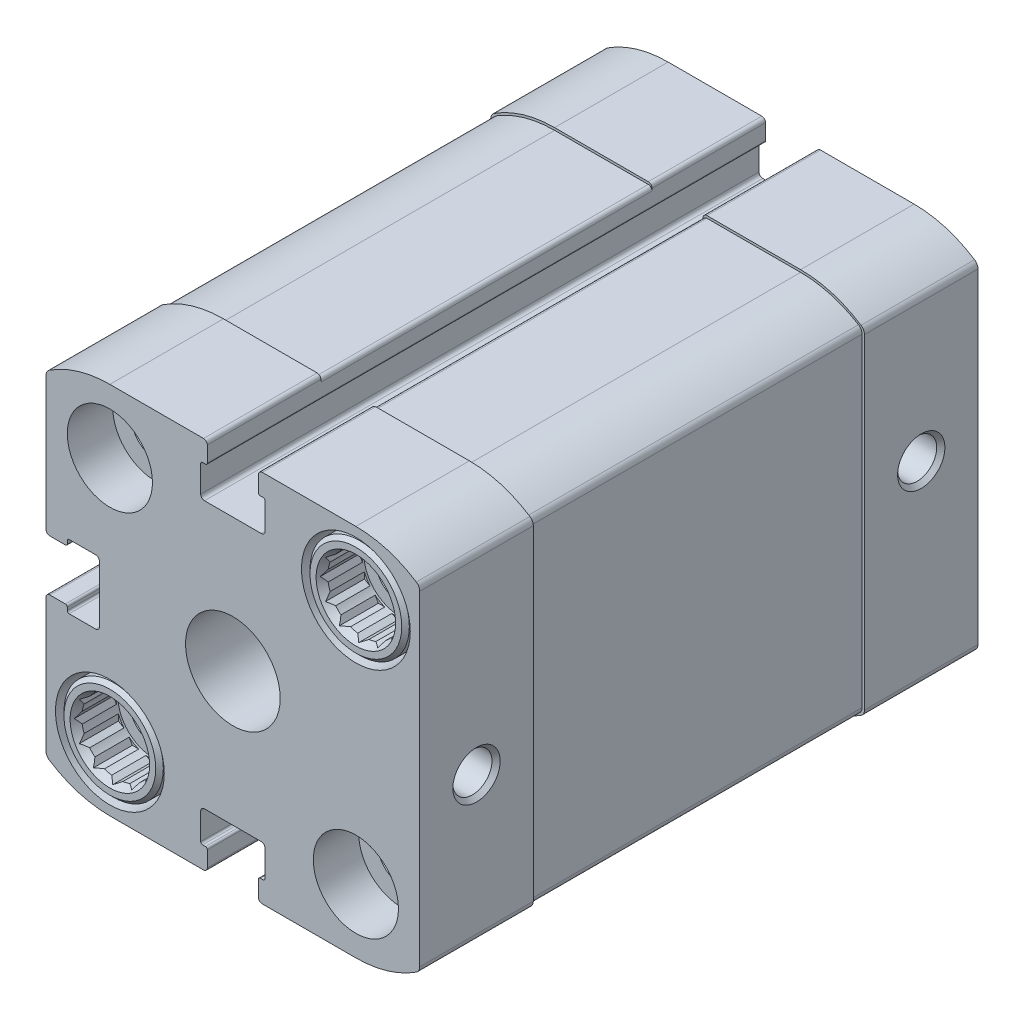
SolidWorks part; units mm, degrees
ref_plane "Ebene vorne" through (0, 0, 0) normal (0, 0, 1) x (1, 0, 0)
ref_plane "Ebene oben" through (0, 0, 0) normal (0, 1, 0) x (1, 0, 0)
ref_plane "Ebene rechts" through (0, 0, 0) normal (1, 0, 0) x (0, 0, -1)
sketch "Skizze1" plane through (0, 0, 0) normal (0, 0, 1) x (1, 0, 0)
  line L0 (-19.75, -3.1) -> (-19.75, -17.1828)
  line L1 (-13, -19.75) -> (-3.1, -19.75)
  line L2 (-2.7, -19.35) -> (-2.7, -17.7)
  line L3 (-2.9, -17.5) -> (-3.2, -17.5)
  line L4 (-3.4, -17.3) -> (-3.4, -14.5)
  line L5 (-3, -14.1) -> (3, -14.1)
  line L6 (3.4, -14.5) -> (3.4, -17.3)
  line L7 (3.2, -17.5) -> (2.9, -17.5)
  line L8 (2.7, -17.7) -> (2.7, -19.35)
  line L9 (3.1, -19.75) -> (13, -19.75)
  line L10 (19.75, -17.1828) -> (19.75, 17.1828)
  line L11 (13, 19.75) -> (3.1, 19.75)
  line L12 (2.7, 19.35) -> (2.7, 17.7)
  line L13 (2.9, 17.5) -> (3.2, 17.5)
  line L14 (3.4, 17.3) -> (3.4, 14.5)
  line L15 (3, 14.1) -> (-3, 14.1)
  line L16 (-3.4, 14.5) -> (-3.4, 17.3)
  line L17 (-3.2, 17.5) -> (-2.9, 17.5)
  line L18 (-2.7, 17.7) -> (-2.7, 19.35)
  line L19 (-3.1, 19.75) -> (-13, 19.75)
  line L20 (-19.75, 17.1828) -> (-19.75, 3.1)
  line L21 (-19.35, 2.7) -> (-17.7, 2.7)
  line L22 (-17.5, 2.9) -> (-17.5, 3.2)
  line L23 (-17.3, 3.4) -> (-14.5, 3.4)
  line L24 (-14.1, 3) -> (-14.1, -3)
  line L25 (-14.5, -3.4) -> (-17.3, -3.4)
  line L26 (-17.5, -3.2) -> (-17.5, -2.9)
  line L27 (-17.7, -2.7) -> (-19.35, -2.7)
  arc A0 (-19.75, -17.1828) -> (-19.3867, -17.8531) centre (-18.95, -17.1828) ccw
  arc A1 (-19.3867, -17.8531) -> (-13, -19.75) centre (-13, -8.05) ccw
  arc A2 (-3.1, -19.75) -> (-2.7, -19.35) centre (-3.1, -19.35) ccw
  arc A3 (-2.7, -17.7) -> (-2.9, -17.5) centre (-2.9, -17.7) ccw
  arc A4 (-3.2, -17.5) -> (-3.4, -17.3) centre (-3.2, -17.3) cw
  arc A5 (-3.4, -14.5) -> (-3, -14.1) centre (-3, -14.5) cw
  arc A6 (3, -14.1) -> (3.4, -14.5) centre (3, -14.5) cw
  arc A7 (3.4, -17.3) -> (3.2, -17.5) centre (3.2, -17.3) cw
  arc A8 (2.9, -17.5) -> (2.7, -17.7) centre (2.9, -17.7) ccw
  arc A9 (2.7, -19.35) -> (3.1, -19.75) centre (3.1, -19.35) ccw
  arc A10 (13, -19.75) -> (19.3867, -17.8531) centre (13, -8.05) ccw
  arc A11 (19.3867, -17.8531) -> (19.75, -17.1828) centre (18.95, -17.1828) ccw
  arc A12 (19.75, 17.1828) -> (19.3867, 17.8531) centre (18.95, 17.1828) ccw
  arc A13 (19.3867, 17.8531) -> (13, 19.75) centre (13, 8.05) ccw
  arc A14 (3.1, 19.75) -> (2.7, 19.35) centre (3.1, 19.35) ccw
  arc A15 (2.7, 17.7) -> (2.9, 17.5) centre (2.9, 17.7) ccw
  arc A16 (3.2, 17.5) -> (3.4, 17.3) centre (3.2, 17.3) cw
  arc A17 (3.4, 14.5) -> (3, 14.1) centre (3, 14.5) cw
  arc A18 (-3, 14.1) -> (-3.4, 14.5) centre (-3, 14.5) cw
  arc A19 (-3.4, 17.3) -> (-3.2, 17.5) centre (-3.2, 17.3) cw
  arc A20 (-2.9, 17.5) -> (-2.7, 17.7) centre (-2.9, 17.7) ccw
  arc A21 (-2.7, 19.35) -> (-3.1, 19.75) centre (-3.1, 19.35) ccw
  arc A22 (-13, 19.75) -> (-19.3867, 17.8531) centre (-13, 8.05) ccw
  arc A23 (-19.3867, 17.8531) -> (-19.75, 17.1828) centre (-18.95, 17.1828) ccw
  arc A24 (-19.75, 3.1) -> (-19.35, 2.7) centre (-19.35, 3.1) ccw
  arc A25 (-17.7, 2.7) -> (-17.5, 2.9) centre (-17.7, 2.9) ccw
  arc A26 (-17.5, 3.2) -> (-17.3, 3.4) centre (-17.3, 3.2) cw
  arc A27 (-14.5, 3.4) -> (-14.1, 3) centre (-14.5, 3) cw
  arc A28 (-14.1, -3) -> (-14.5, -3.4) centre (-14.5, -3) cw
  arc A29 (-17.3, -3.4) -> (-17.5, -3.2) centre (-17.3, -3.2) cw
  arc A30 (-17.5, -2.9) -> (-17.7, -2.7) centre (-17.7, -2.9) ccw
  arc A31 (-19.35, -2.7) -> (-19.75, -3.1) centre (-19.35, -3.1) ccw
extrude "Aufsatz-Linear austragen1" add sketch "Skizze1" against normal blind 59
ref_plane "Ebene1" through (0, 0, -12) normal (0, 0, 1) x (1, 0, 0)
sketch "Skizze2" plane through (0, 0, -12) normal (0, 0, 1) x (1, 0, 0)
  line L0 (-39.5, 39.5) -> (-39.5, -39.5)
  line L1 (-39.5, -39.5) -> (39.5, -39.5)
  line L2 (39.5, -39.5) -> (39.5, 39.5)
  line L3 (39.5, 39.5) -> (-39.5, 39.5)
  line L4 (-19.5, -3.1) -> (-19.5, -17.0909)
  line L5 (-13, -19.5) -> (-3.1, -19.5)
  line L6 (-2.7, -19.1) -> (-2.7, -17.65)
  line L7 (-2.85, -17.5) -> (-3.2, -17.5)
  line L8 (-3.4, -17.3) -> (-3.4, -14.5)
  line L9 (-3, -14.1) -> (3, -14.1)
  line L10 (3.4, -14.5) -> (3.4, -17.3)
  line L11 (3.2, -17.5) -> (2.85, -17.5)
  line L12 (2.7, -17.65) -> (2.7, -19.1)
  line L13 (3.1, -19.5) -> (13, -19.5)
  line L14 (19.5, -17.0909) -> (19.5, 17.0909)
  line L15 (13, 19.5) -> (3.1, 19.5)
  line L16 (2.7, 19.1) -> (2.7, 17.65)
  line L17 (2.85, 17.5) -> (3.2, 17.5)
  line L18 (3.4, 17.3) -> (3.4, 14.5)
  line L19 (3, 14.1) -> (-3, 14.1)
  line L20 (-3.4, 14.5) -> (-3.4, 17.3)
  line L21 (-3.2, 17.5) -> (-2.85, 17.5)
  line L22 (-2.7, 17.65) -> (-2.7, 19.1)
  line L23 (-3.1, 19.5) -> (-13, 19.5)
  line L24 (-19.5, 17.0909) -> (-19.5, 3.1)
  line L25 (-19.1, 2.7) -> (-17.65, 2.7)
  line L26 (-17.5, 2.85) -> (-17.5, 3.2)
  line L27 (-17.3, 3.4) -> (-14.5, 3.4)
  line L28 (-14.1, 3) -> (-14.1, -3)
  line L29 (-14.5, -3.4) -> (-17.3, -3.4)
  line L30 (-17.5, -3.2) -> (-17.5, -2.85)
  line L31 (-17.65, -2.7) -> (-19.1, -2.7)
  arc A0 (-19.5, -17.0909) -> (-19.1183, -17.7728) centre (-18.7, -17.0909) ccw
  arc A1 (-19.1183, -17.7728) -> (-13, -19.5) centre (-13, -7.8) ccw
  arc A2 (-3.1, -19.5) -> (-2.7, -19.1) centre (-3.1, -19.1) ccw
  arc A3 (-2.7, -17.65) -> (-2.85, -17.5) centre (-2.85, -17.65) ccw
  arc A4 (-3.2, -17.5) -> (-3.4, -17.3) centre (-3.2, -17.3) cw
  arc A5 (-3.4, -14.5) -> (-3, -14.1) centre (-3, -14.5) cw
  arc A6 (3, -14.1) -> (3.4, -14.5) centre (3, -14.5) cw
  arc A7 (3.4, -17.3) -> (3.2, -17.5) centre (3.2, -17.3) cw
  arc A8 (2.85, -17.5) -> (2.7, -17.65) centre (2.85, -17.65) ccw
  arc A9 (2.7, -19.1) -> (3.1, -19.5) centre (3.1, -19.1) ccw
  arc A10 (13, -19.5) -> (19.1183, -17.7728) centre (13, -7.8) ccw
  arc A11 (19.1183, -17.7728) -> (19.5, -17.0909) centre (18.7, -17.0909) ccw
  arc A12 (19.5, 17.0909) -> (19.1183, 17.7728) centre (18.7, 17.0909) ccw
  arc A13 (19.1183, 17.7728) -> (13, 19.5) centre (13, 7.8) ccw
  arc A14 (3.1, 19.5) -> (2.7, 19.1) centre (3.1, 19.1) ccw
  arc A15 (2.7, 17.65) -> (2.85, 17.5) centre (2.85, 17.65) ccw
  arc A16 (3.2, 17.5) -> (3.4, 17.3) centre (3.2, 17.3) cw
  arc A17 (3.4, 14.5) -> (3, 14.1) centre (3, 14.5) cw
  arc A18 (-3, 14.1) -> (-3.4, 14.5) centre (-3, 14.5) cw
  arc A19 (-3.4, 17.3) -> (-3.2, 17.5) centre (-3.2, 17.3) cw
  arc A20 (-2.85, 17.5) -> (-2.7, 17.65) centre (-2.85, 17.65) ccw
  arc A21 (-2.7, 19.1) -> (-3.1, 19.5) centre (-3.1, 19.1) ccw
  arc A22 (-13, 19.5) -> (-19.1183, 17.7728) centre (-13, 7.8) ccw
  arc A23 (-19.1183, 17.7728) -> (-19.5, 17.0909) centre (-18.7, 17.0909) ccw
  arc A24 (-19.5, 3.1) -> (-19.1, 2.7) centre (-19.1, 3.1) ccw
  arc A25 (-17.65, 2.7) -> (-17.5, 2.85) centre (-17.65, 2.85) ccw
  arc A26 (-17.5, 3.2) -> (-17.3, 3.4) centre (-17.3, 3.2) cw
  arc A27 (-14.5, 3.4) -> (-14.1, 3) centre (-14.5, 3) cw
  arc A28 (-14.1, -3) -> (-14.5, -3.4) centre (-14.5, -3) cw
  arc A29 (-17.3, -3.4) -> (-17.5, -3.2) centre (-17.3, -3.2) cw
  arc A30 (-17.5, -2.85) -> (-17.65, -2.7) centre (-17.65, -2.85) ccw
  arc A31 (-19.1, -2.7) -> (-19.5, -3.1) centre (-19.1, -3.1) ccw
extrude "Schnitt-Linear austragen1" cut sketch "Skizze2" against normal blind 35
ref_plane "Ebene2" through (0, 0, -47) normal (0, 0, 1) x (1, 0, 0)
ref_plane "Ebene3" through (0, -2.6, 0) normal (0, 1, 0) x (1, 0, 0)
ref_plane "Ebene4" through (0, 2.6, 0) normal (0, 1, 0) x (1, 0, 0)
hole_wizard "Bohrung1" positions "Skizze4" profile "Skizze3" legacy
sketch "Skizze4" plane through (19.75, 0, 0) normal (1, 0, 0) x (0, 0, -1)
  point P0 (6, -2.6)
sketch "Skizze3" plane through (19.75, -2.6, -6) normal (0, 1, 0) x (0, 0, -1)
  line L0 (0, 0) -> (0, 11)
  line L1 (0, 11) -> (2.067, 11)
  line L2 (2.067, 11) -> (2.067, 0.433)
  line L3 (2.067, 0.433) -> (2.5, 0)
  line L4 (2.5, 0) -> (0, 0)
  line L5 (0, -6.4453) -> (0, 115.525) construction
  line L6 (-2.067, 0.433) -> (-2.5, 0) construction
  dimension "Durchmesser" = 4.134
  dimension "Tiefe" = 11
  dimension "Senkwinkel1" = 90
  dimension "Senkdurchmesser3" = 5
cosmetic thread "Gewindedarstellung1" parameters "D1"=5.5, "D2"=5
ref_plane "Ebene5" through (19.75, 0, 0) normal (1, 0, 0) x (0, 0, -1)
hole_wizard "Bohrung2" positions "Skizze6" profile "Skizze5" legacy
sketch "Skizze6" plane through (19.75, 0, 0) normal (1, 0, 0) x (0, 0, -1)
  point P0 (53, 2.6)
sketch "Skizze5" plane through (19.75, 2.6, -53) normal (0, 1, 0) x (0, 0, -1)
  line L0 (0, 0) -> (0, 11)
  line L1 (0, 11) -> (2.067, 11)
  line L2 (2.067, 11) -> (2.067, 0.433)
  line L3 (2.067, 0.433) -> (2.5, 0)
  line L4 (2.5, 0) -> (0, 0)
  line L5 (0, -6.4453) -> (0, 115.525) construction
  line L6 (-2.067, 0.433) -> (-2.5, 0) construction
  dimension "Durchmesser" = 4.134
  dimension "Tiefe" = 11
  dimension "Senkwinkel1" = 90
  dimension "Senkdurchmesser3" = 5
cosmetic thread "Gewindedarstellung2" parameters "D1"=5.5, "D2"=5
sketch "Skizze7" plane through (0, 0, 0) normal (1, 0, 0) x (0, 0, -1)
  line L0 (-12.2, 0) -> (-12.2, 5)
  line L1 (-12.2, 5) -> (20.75, 5)
  line L2 (20.75, 5) -> (20.75, 12.5)
  line L3 (20.75, 12.5) -> (47, 12.5)
  line L4 (47, 12.5) -> (47, 0)
  line L5 (47, 0) -> (-12.2, 0)
  line L6 (47, 0) -> (-12.2, 0) construction
revolve "Schnitt-Rotation1" cut sketch "Skizze7" angle 360 about L6 reverse direction yes
hole_wizard "Bohrung3" positions "Skizze9" profile "Skizze8" legacy
sketch "Skizze9" plane through (0, 0, -59) normal (0, 0, -1) x (-1, 0, 0)
  point P0 (0, 0)
sketch "Skizze8" plane through (0, 0, -59) normal (1, 0, 0) x (0, 1, 0)
  line L0 (0, 0) -> (0, 2.1)
  line L1 (0, 2.1) -> (4.5, 2.1)
  line L2 (4.5, 2.1) -> (4.5, 0)
  line L3 (4.5, 0) -> (0, 0)
  line L4 (0, 110) -> (0, -10) construction
  dimension "Durchmesser" = 9
  dimension "Tiefe" = 2.1
ref_plane "Ebene6" through (13, 0, 0) normal (1, 0, 0) x (0, 0, -1)
ref_plane "Ebene7" through (-13, 0, 0) normal (1, 0, 0) x (0, 0, -1)
hole_wizard "Bohrung4" positions "Skizze11" profile "Skizze10" legacy
sketch "Skizze11" plane through (0, 0, 0) normal (0, 0, 1) x (1, 0, 0)
  point P0 (13, 13)
sketch "Skizze10" plane through (13, 13, 0) normal (1, 0, 0) x (0, -1, 0)
  line L0 (0, 0) -> (0, 19.5)
  line L1 (0, 19.5) -> (3.5, 19.5)
  line L2 (3.5, 19.5) -> (3.5, 6.5)
  line L3 (3.5, 6.5) -> (5.75, 6.5)
  line L4 (5.75, 6.5) -> (5.75, 0)
  line L5 (5.75, 0) -> (0, 0)
  line L6 (0, 110) -> (0, -10) construction
  dimension "Durchmesser" = 7
  dimension "Tiefe" = 19.5
  dimension "Senkdurchmesser1" = 11.5
  dimension "Senktiefe1" = 6.5
sketch "Skizze12" plane through (13, 0, 0) normal (1, 0, 0) x (0, 0, -1)
  line L0 (0, 17.2) -> (0.7794, 16.75)
  line L1 (0.7794, 16.75) -> (4.6, 16.75)
  line L2 (4.6, 16.75) -> (4.6, 15.5)
  line L3 (4.6, 15.5) -> (5.033, 15.067)
  line L4 (5.033, 15.067) -> (19.5, 15.067)
  line L5 (19.5, 15.067) -> (19.5, 17.5)
  line L6 (19.5, 17.5) -> (6.5, 17.5)
  line L7 (6.5, 17.5) -> (6.5, 18.25)
  line L8 (6.5, 18.25) -> (0.4, 18.25)
  line L9 (0.4, 18.25) -> (0, 17.85)
  line L10 (0, 17.85) -> (0, 17.2)
  line L11 (19.5, 13) -> (0, 13) construction
revolve "Rotation1" add sketch "Skizze12" angle 360 about L11 reverse direction yes
cosmetic thread "Gewindedarstellung3" parameters "D1"=14.9, "D2"=5
hole_wizard "Bohrung5" positions "Skizze14" profile "Skizze13" legacy
sketch "Skizze14" plane through (0, 0, -59) normal (0, 0, -1) x (-1, 0, 0)
  point P0 (-13, -13)
sketch "Skizze13" plane through (13, -13, -59) normal (1, 0, 0) x (0, 1, 0)
  line L0 (0, 0) -> (0, 19.5)
  line L1 (0, 19.5) -> (3.5, 19.5)
  line L2 (3.5, 19.5) -> (3.5, 6.5)
  line L3 (3.5, 6.5) -> (5.75, 6.5)
  line L4 (5.75, 6.5) -> (5.75, 0)
  line L5 (5.75, 0) -> (0, 0)
  line L6 (0, 110) -> (0, -10) construction
  dimension "Durchmesser" = 7
  dimension "Tiefe" = 19.5
  dimension "Senkdurchmesser1" = 11.5
  dimension "Senktiefe1" = 6.5
sketch "Skizze15" plane through (13, 0, 0) normal (1, 0, 0) x (0, 0, -1)
  line L0 (39.5, -8.5) -> (39.5, -10.933)
  line L1 (39.5, -10.933) -> (53.967, -10.933)
  line L2 (53.967, -10.933) -> (54.4, -10.5)
  line L3 (54.4, -10.5) -> (54.4, -9.25)
  line L4 (54.4, -9.25) -> (58.2206, -9.25)
  line L5 (58.2206, -9.25) -> (59, -8.8)
  line L6 (59, -8.8) -> (59, -8.15)
  line L7 (59, -8.15) -> (58.6, -7.75)
  line L8 (58.6, -7.75) -> (52.5, -7.75)
  line L9 (52.5, -7.75) -> (52.5, -8.5)
  line L10 (52.5, -8.5) -> (39.5, -8.5)
  line L11 (59, -13) -> (39.5, -13) construction
revolve "Rotation2" add sketch "Skizze15" angle 360 about L11 reverse direction yes
cosmetic thread "Gewindedarstellung4" parameters "D1"=49.167, "D2"=5
cosmetic thread "Gewindedarstellung7" parameters "D1"=7.2, "D2"=5
hole_wizard "Bohrung6" positions "Skizze17" profile "Skizze16" legacy
sketch "Skizze17" plane through (0, 0, 0) normal (0, 0, 1) x (1, 0, 0)
  point P0 (-13, -13)
sketch "Skizze16" plane through (-13, -13, 0) normal (1, 0, 0) x (0, -1, 0)
  line L0 (0, 0) -> (0, 19.5)
  line L1 (0, 19.5) -> (3.5, 19.5)
  line L2 (3.5, 19.5) -> (3.5, 6.5)
  line L3 (3.5, 6.5) -> (5.75, 6.5)
  line L4 (5.75, 6.5) -> (5.75, 0)
  line L5 (5.75, 0) -> (0, 0)
  line L6 (0, 110) -> (0, -10) construction
  dimension "Durchmesser" = 7
  dimension "Tiefe" = 19.5
  dimension "Senkdurchmesser1" = 11.5
  dimension "Senktiefe1" = 6.5
hole_wizard "Bohrung7" positions "Skizze19" profile "Skizze18" legacy
sketch "Skizze19" plane through (0, 0, -59) normal (0, 0, -1) x (-1, 0, 0)
  point P0 (13, 13)
sketch "Skizze18" plane through (-13, 13, -59) normal (1, 0, 0) x (0, 1, 0)
  line L0 (0, 0) -> (0, 19.5)
  line L1 (0, 19.5) -> (3.5, 19.5)
  line L2 (3.5, 19.5) -> (3.5, 6.5)
  line L3 (3.5, 6.5) -> (5.75, 6.5)
  line L4 (5.75, 6.5) -> (5.75, 0)
  line L5 (5.75, 0) -> (0, 0)
  line L6 (0, 110) -> (0, -10) construction
  dimension "Durchmesser" = 7
  dimension "Tiefe" = 19.5
  dimension "Senkdurchmesser1" = 11.5
  dimension "Senktiefe1" = 6.5
sketch "Skizze20" plane through (-13, 0, 0) normal (1, 0, 0) x (0, 0, -1)
  line L0 (0, -8.8) -> (0.7794, -9.25)
  line L1 (0.7794, -9.25) -> (4.6, -9.25)
  line L2 (4.6, -9.25) -> (4.6, -10.5)
  line L3 (4.6, -10.5) -> (5.033, -10.933)
  line L4 (5.033, -10.933) -> (19.5, -10.933)
  line L5 (19.5, -10.933) -> (19.5, -8.5)
  line L6 (19.5, -8.5) -> (6.5, -8.5)
  line L7 (6.5, -8.5) -> (6.5, -7.75)
  line L8 (6.5, -7.75) -> (0.4, -7.75)
  line L9 (0.4, -7.75) -> (0, -8.15)
  line L10 (0, -8.15) -> (0, -8.8)
  line L11 (19.5, -13) -> (0, -13) construction
revolve "Rotation3" add sketch "Skizze20" angle 360 about L11 reverse direction yes
cosmetic thread "Gewindedarstellung5" parameters "D1"=14.9, "D2"=5
sketch "Skizze21" plane through (-13, 0, 0) normal (1, 0, 0) x (0, 0, -1)
  line L0 (39.5, 17.5) -> (39.5, 15.067)
  line L1 (39.5, 15.067) -> (53.967, 15.067)
  line L2 (53.967, 15.067) -> (54.4, 15.5)
  line L3 (54.4, 15.5) -> (54.4, 16.75)
  line L4 (54.4, 16.75) -> (58.2206, 16.75)
  line L5 (58.2206, 16.75) -> (59, 17.2)
  line L6 (59, 17.2) -> (59, 17.85)
  line L7 (59, 17.85) -> (58.6, 18.25)
  line L8 (58.6, 18.25) -> (52.5, 18.25)
  line L9 (52.5, 18.25) -> (52.5, 17.5)
  line L10 (52.5, 17.5) -> (39.5, 17.5)
  line L11 (59, 13) -> (39.5, 13) construction
revolve "Rotation4" add sketch "Skizze21" angle 360 about L11 reverse direction yes
cosmetic thread "Gewindedarstellung6" parameters "D1"=49.167, "D2"=5
cosmetic thread "Gewindedarstellung9" parameters "D1"=7.2, "D2"=5
sketch "Skizze22" plane through (13, 0, 0) normal (1, 0, 0) x (0, 0, -1)
  line L0 (-0.1, -13) -> (-0.1, -8.5)
  line L1 (-0.1, -8.5) -> (4.8, -8.5)
  line L2 (4.8, -8.5) -> (4.8, -10.5)
  line L3 (4.8, -10.5) -> (5.233, -10.933)
  line L4 (5.233, -10.933) -> (39.5, -10.933)
  line L5 (39.5, -10.933) -> (39.5, -13)
  line L6 (39.5, -13) -> (-0.1, -13)
  line L7 (39.5, -13) -> (-0.1, -13) construction
revolve "Schnitt-Rotation2" cut sketch "Skizze22" angle 360 about L7 reverse direction yes
sketch "Skizze23" plane through (13, 0, 0) normal (1, 0, 0) x (0, 0, -1)
  line L0 (12, -13) -> (12, -8.5)
  line L1 (12, -8.5) -> (39.5, -8.5)
  line L2 (39.5, -8.5) -> (39.5, -13)
  line L3 (39.5, -13) -> (12, -13)
  line L4 (39.5, -13) -> (12, -13) construction
revolve "Rotation5" add sketch "Skizze23" angle 360 about L4 reverse direction yes
hole_wizard "Bohrung8" positions "Skizze25" profile "Skizze24" legacy
sketch "Skizze25" plane through (0, 0, -39.5) normal (0, 0, -1) x (-1, 0, 0)
  point P0 (-13, -13)
sketch "Skizze24" plane through (13, -13, -39.5) normal (1, 0, 0) x (0, 1, 0)
  line L0 (0, 0) -> (0, 27.5)
  line L1 (0, 27.5) -> (2.5, 27.5)
  line L2 (2.5, 27.5) -> (2.5, 0)
  line L3 (2.5, 0) -> (0, 0)
  line L4 (0, 110) -> (0, -10) construction
  dimension "Durchmesser" = 5
  dimension "Tiefe" = 27.5
sketch "Skizze26" plane through (13, 0, 0) normal (1, 0, 0) x (0, 0, -1)
  line L0 (29.5, 13) -> (29.5, 15.067)
  line L1 (29.5, 15.067) -> (53.767, 15.067)
  line L2 (53.767, 15.067) -> (54.2, 15.5)
  line L3 (54.2, 15.5) -> (54.2, 17.5)
  line L4 (54.2, 17.5) -> (59.1, 17.5)
  line L5 (59.1, 17.5) -> (59.1, 13)
  line L6 (59.1, 13) -> (29.5, 13)
  line L7 (59.1, 13) -> (29.5, 13) construction
revolve "Schnitt-Rotation3" cut sketch "Skizze26" angle 360 about L7 reverse direction yes
cosmetic thread "Gewindedarstellung8" parameters "D1"=7.2, "D2"=5
sketch "Skizze27" plane through (13, 0, 0) normal (1, 0, 0) x (0, 0, -1)
  line L0 (19.5, 13) -> (19.5, 17.5)
  line L1 (19.5, 17.5) -> (47, 17.5)
  line L2 (47, 17.5) -> (47, 13)
  line L3 (47, 13) -> (19.5, 13)
  line L4 (47, 13) -> (19.5, 13) construction
revolve "Rotation6" add sketch "Skizze27" angle 360 about L4 reverse direction yes
hole_wizard "Bohrung9" positions "Skizze29" profile "Skizze28" legacy
sketch "Skizze29" plane through (0, 0, -47) normal (0, 0, -1) x (-1, 0, 0)
  point P0 (-13, 13)
sketch "Skizze28" plane through (13, 13, -47) normal (1, 0, 0) x (0, 1, 0)
  line L0 (0, 0) -> (0, 27.5)
  line L1 (0, 27.5) -> (2.5, 27.5)
  line L2 (2.5, 27.5) -> (2.5, 0)
  line L3 (2.5, 0) -> (0, 0)
  line L4 (0, 110) -> (0, -10) construction
  dimension "Durchmesser" = 5
  dimension "Tiefe" = 27.5
sketch "Skizze30" plane through (-13, 0, 0) normal (1, 0, 0) x (0, 0, -1)
  line L0 (-0.1, 13) -> (-0.1, 17.5)
  line L1 (-0.1, 17.5) -> (4.8, 17.5)
  line L2 (4.8, 17.5) -> (4.8, 15.5)
  line L3 (4.8, 15.5) -> (5.233, 15.067)
  line L4 (5.233, 15.067) -> (39.5, 15.067)
  line L5 (39.5, 15.067) -> (39.5, 13)
  line L6 (39.5, 13) -> (-0.1, 13)
  line L7 (39.5, 13) -> (-0.1, 13) construction
revolve "Schnitt-Rotation4" cut sketch "Skizze30" angle 360 about L7 reverse direction yes
sketch "Skizze31" plane through (-13, 0, 0) normal (1, 0, 0) x (0, 0, -1)
  line L0 (12, 13) -> (12, 17.5)
  line L1 (12, 17.5) -> (39.5, 17.5)
  line L2 (39.5, 17.5) -> (39.5, 13)
  line L3 (39.5, 13) -> (12, 13)
  line L4 (39.5, 13) -> (12, 13) construction
revolve "Rotation7" add sketch "Skizze31" angle 360 about L4 reverse direction yes
hole_wizard "Bohrung10" positions "Skizze33" profile "Skizze32" legacy
sketch "Skizze33" plane through (0, 0, -39.5) normal (0, 0, -1) x (-1, 0, 0)
  point P0 (13, 13)
sketch "Skizze32" plane through (-13, 13, -39.5) normal (1, 0, 0) x (0, 1, 0)
  line L0 (0, 0) -> (0, 27.5)
  line L1 (0, 27.5) -> (2.5, 27.5)
  line L2 (2.5, 27.5) -> (2.5, 0)
  line L3 (2.5, 0) -> (0, 0)
  line L4 (0, 110) -> (0, -10) construction
  dimension "Durchmesser" = 5
  dimension "Tiefe" = 27.5
sketch "Skizze34" plane through (-13, 0, 0) normal (1, 0, 0) x (0, 0, -1)
  line L0 (29.5, -13) -> (29.5, -10.933)
  line L1 (29.5, -10.933) -> (53.767, -10.933)
  line L2 (53.767, -10.933) -> (54.2, -10.5)
  line L3 (54.2, -10.5) -> (54.2, -8.5)
  line L4 (54.2, -8.5) -> (59.1, -8.5)
  line L5 (59.1, -8.5) -> (59.1, -13)
  line L6 (59.1, -13) -> (29.5, -13)
  line L7 (59.1, -13) -> (29.5, -13) construction
revolve "Schnitt-Rotation5" cut sketch "Skizze34" angle 360 about L7 reverse direction yes
cosmetic thread "Gewindedarstellung10" parameters "D1"=7.2, "D2"=5
sketch "Skizze35" plane through (-13, 0, 0) normal (1, 0, 0) x (0, 0, -1)
  line L0 (19.5, -13) -> (19.5, -8.5)
  line L1 (19.5, -8.5) -> (47, -8.5)
  line L2 (47, -8.5) -> (47, -13)
  line L3 (47, -13) -> (19.5, -13)
  line L4 (47, -13) -> (19.5, -13) construction
revolve "Rotation8" add sketch "Skizze35" angle 360 about L4 reverse direction yes
hole_wizard "Bohrung11" positions "Skizze37" profile "Skizze36" legacy
sketch "Skizze37" plane through (0, 0, -47) normal (0, 0, -1) x (-1, 0, 0)
  point P0 (13, -13)
sketch "Skizze36" plane through (-13, -13, -47) normal (1, 0, 0) x (0, 1, 0)
  line L0 (0, 0) -> (0, 27.5)
  line L1 (0, 27.5) -> (2.5, 27.5)
  line L2 (2.5, 27.5) -> (2.5, 0)
  line L3 (2.5, 0) -> (0, 0)
  line L4 (0, 110) -> (0, -10) construction
  dimension "Durchmesser" = 5
  dimension "Tiefe" = 27.5
sketch "Skizze38" plane through (0, 0, 0) normal (0, 0, 1) x (1, 0, 0)
  line L0 (-17.0415, -13) -> (-16.5, -13.9378)
  line L1 (-16.5, -13.9378) -> (-16.5, -15.0207)
  line L2 (-16.5, -15.0207) -> (-15.5622, -15.5622)
  line L3 (-15.5622, -15.5622) -> (-15.0207, -16.5)
  line L4 (-15.0207, -16.5) -> (-13.9378, -16.5)
  line L5 (-13.9378, -16.5) -> (-13, -17.0415)
  line L6 (-13, -17.0415) -> (-12.0622, -16.5)
  line L7 (-12.0622, -16.5) -> (-10.9793, -16.5)
  line L8 (-10.9793, -16.5) -> (-10.4378, -15.5622)
  line L9 (-10.4378, -15.5622) -> (-9.5, -15.0207)
  line L10 (-9.5, -15.0207) -> (-9.5, -13.9378)
  line L11 (-9.5, -13.9378) -> (-8.9585, -13)
  line L12 (-8.9585, -13) -> (-9.5, -12.0622)
  line L13 (-9.5, -12.0622) -> (-9.5, -10.9793)
  line L14 (-9.5, -10.9793) -> (-10.4378, -10.4378)
  line L15 (-10.4378, -10.4378) -> (-10.9793, -9.5)
  line L16 (-10.9793, -9.5) -> (-12.0622, -9.5)
  line L17 (-12.0622, -9.5) -> (-13, -8.9585)
  line L18 (-13, -8.9585) -> (-13.9378, -9.5)
  line L19 (-13.9378, -9.5) -> (-15.0207, -9.5)
  line L20 (-15.0207, -9.5) -> (-15.5622, -10.4378)
  line L21 (-15.5622, -10.4378) -> (-16.5, -10.9793)
  line L22 (-16.5, -10.9793) -> (-16.5, -12.0622)
  line L23 (-16.5, -12.0622) -> (-17.0415, -13)
extrude "Schnitt-Linear austragen2" cut sketch "Skizze38" against normal blind 4.4
sketch "Skizze39" plane through (0, 0, 0) normal (0, 0, 1) x (1, 0, 0)
  line L0 (8.9585, 13) -> (9.5, 12.0622)
  line L1 (9.5, 12.0622) -> (9.5, 10.9793)
  line L2 (9.5, 10.9793) -> (10.4378, 10.4378)
  line L3 (10.4378, 10.4378) -> (10.9793, 9.5)
  line L4 (10.9793, 9.5) -> (12.0622, 9.5)
  line L5 (12.0622, 9.5) -> (13, 8.9585)
  line L6 (13, 8.9585) -> (13.9378, 9.5)
  line L7 (13.9378, 9.5) -> (15.0207, 9.5)
  line L8 (15.0207, 9.5) -> (15.5622, 10.4378)
  line L9 (15.5622, 10.4378) -> (16.5, 10.9793)
  line L10 (16.5, 10.9793) -> (16.5, 12.0622)
  line L11 (16.5, 12.0622) -> (17.0415, 13)
  line L12 (17.0415, 13) -> (16.5, 13.9378)
  line L13 (16.5, 13.9378) -> (16.5, 15.0207)
  line L14 (16.5, 15.0207) -> (15.5622, 15.5622)
  line L15 (15.5622, 15.5622) -> (15.0207, 16.5)
  line L16 (15.0207, 16.5) -> (13.9378, 16.5)
  line L17 (13.9378, 16.5) -> (13, 17.0415)
  line L18 (13, 17.0415) -> (12.0622, 16.5)
  line L19 (12.0622, 16.5) -> (10.9793, 16.5)
  line L20 (10.9793, 16.5) -> (10.4378, 15.5622)
  line L21 (10.4378, 15.5622) -> (9.5, 15.0207)
  line L22 (9.5, 15.0207) -> (9.5, 13.9378)
  line L23 (9.5, 13.9378) -> (8.9585, 13)
extrude "Schnitt-Linear austragen3" cut sketch "Skizze39" against normal blind 4.4
ref_plane "Ebene8" through (0, 0, -59) normal (0, 0, 1) x (1, 0, 0)
sketch "Skizze40" plane through (0, 0, -59) normal (0, 0, 1) x (1, 0, 0)
  line L0 (-17.0415, 13) -> (-16.5, 12.0622)
  line L1 (-16.5, 12.0622) -> (-16.5, 10.9793)
  line L2 (-16.5, 10.9793) -> (-15.5622, 10.4378)
  line L3 (-15.5622, 10.4378) -> (-15.0207, 9.5)
  line L4 (-15.0207, 9.5) -> (-13.9378, 9.5)
  line L5 (-13.9378, 9.5) -> (-13, 8.9585)
  line L6 (-13, 8.9585) -> (-12.0622, 9.5)
  line L7 (-12.0622, 9.5) -> (-10.9793, 9.5)
  line L8 (-10.9793, 9.5) -> (-10.4378, 10.4378)
  line L9 (-10.4378, 10.4378) -> (-9.5, 10.9793)
  line L10 (-9.5, 10.9793) -> (-9.5, 12.0622)
  line L11 (-9.5, 12.0622) -> (-8.9585, 13)
  line L12 (-8.9585, 13) -> (-9.5, 13.9378)
  line L13 (-9.5, 13.9378) -> (-9.5, 15.0207)
  line L14 (-9.5, 15.0207) -> (-10.4378, 15.5622)
  line L15 (-10.4378, 15.5622) -> (-10.9793, 16.5)
  line L16 (-10.9793, 16.5) -> (-12.0622, 16.5)
  line L17 (-12.0622, 16.5) -> (-13, 17.0415)
  line L18 (-13, 17.0415) -> (-13.9378, 16.5)
  line L19 (-13.9378, 16.5) -> (-15.0207, 16.5)
  line L20 (-15.0207, 16.5) -> (-15.5622, 15.5622)
  line L21 (-15.5622, 15.5622) -> (-16.5, 15.0207)
  line L22 (-16.5, 15.0207) -> (-16.5, 13.9378)
  line L23 (-16.5, 13.9378) -> (-17.0415, 13)
extrude "Schnitt-Linear austragen4" cut sketch "Skizze40" along normal blind 4.4
sketch "Skizze41" plane through (0, 0, -59) normal (0, 0, 1) x (1, 0, 0)
  line L0 (8.9585, -13) -> (9.5, -13.9378)
  line L1 (9.5, -13.9378) -> (9.5, -15.0207)
  line L2 (9.5, -15.0207) -> (10.4378, -15.5622)
  line L3 (10.4378, -15.5622) -> (10.9793, -16.5)
  line L4 (10.9793, -16.5) -> (12.0622, -16.5)
  line L5 (12.0622, -16.5) -> (13, -17.0415)
  line L6 (13, -17.0415) -> (13.9378, -16.5)
  line L7 (13.9378, -16.5) -> (15.0207, -16.5)
  line L8 (15.0207, -16.5) -> (15.5622, -15.5622)
  line L9 (15.5622, -15.5622) -> (16.5, -15.0207)
  line L10 (16.5, -15.0207) -> (16.5, -13.9378)
  line L11 (16.5, -13.9378) -> (17.0415, -13)
  line L12 (17.0415, -13) -> (16.5, -12.0622)
  line L13 (16.5, -12.0622) -> (16.5, -10.9793)
  line L14 (16.5, -10.9793) -> (15.5622, -10.4378)
  line L15 (15.5622, -10.4378) -> (15.0207, -9.5)
  line L16 (15.0207, -9.5) -> (13.9378, -9.5)
  line L17 (13.9378, -9.5) -> (13, -8.9585)
  line L18 (13, -8.9585) -> (12.0622, -9.5)
  line L19 (12.0622, -9.5) -> (10.9793, -9.5)
  line L20 (10.9793, -9.5) -> (10.4378, -10.4378)
  line L21 (10.4378, -10.4378) -> (9.5, -10.9793)
  line L22 (9.5, -10.9793) -> (9.5, -12.0622)
  line L23 (9.5, -12.0622) -> (8.9585, -13)
extrude "Schnitt-Linear austragen5" cut sketch "Skizze41" along normal blind 4.4
ref_plane "Ebene9" through (0, 0, -47) normal (0, 0, 1) x (1, 0, 0)
ref_plane "Ebene10" through (19.75, 0, 0) normal (1, 0, 0) x (0, 0, -1)
ref_plane "Ebene11" through (0, 0, -59) normal (0, 0, 1) x (1, 0, 0)
ref_plane "Ebene12" through (0, 0, 0) normal (0, 0, 1) x (1, 0, 0)
ref_plane "Ebene13" through (0, 0, 0) normal (0, 0, 1) x (1, 0, 0)
ref_plane "Ebene14" through (0, 0, 0) normal (1, 0, 0) x (0, 0, -1)
ref_plane "Ebene15" through (19.75, 0, 0) normal (1, 0, 0) x (0, 0, -1)
ref_plane "CYLINDER XY" through (0, 0, -47) normal (0, 0, 1) x (1, 0, 0)
ref_plane "CYLINDER XZ" through (0, 0, 0) normal (0, -1, 0) x (-1, 0, 0)
ref_plane "CYLINDER YZ" through (0, 0, 0) normal (1, 0, 0) x (0, 0, -1)
ref_axis "CYLINDER X" through (-80.9, 0, -47) along (1, 0, 0)
ref_axis "CYLINDER Y" through (0, -50, -47) along (0, 1, 0)
ref_axis "CYLINDER Z" through (0, 0, 80.9) along (0, 0, -1)
sketch3d "CYLINDER"
  point P0 (0, 0, -47)
ref_plane "FDT_FRONT XY" through (0, 0, 0) normal (0, 0, 1) x (1, 0, 0)
ref_plane "FDT_FRONT XZ" through (0, 0, 0) normal (-1, 0, 0) x (0, 0, 1)
ref_plane "FDT_FRONT YZ" through (0, 0, 0) normal (0, -1, 0) x (-1, 0, 0)
ref_axis "FDT_FRONT X" through (0, 50, 0) along (0, -1, 0)
ref_axis "FDT_FRONT Y" through (-80.9, 0, 0) along (1, 0, 0)
ref_axis "FDT_FRONT Z" through (0, 0, 50) along (0, 0, -1)
sketch3d "FDT_FRONT"
  point P0 (0, 0, 0)
ref_plane "FDT_QSFRONT XY" through (19.75, 0, 0) normal (1, 0, 0) x (0, 0, -1)
ref_plane "FDT_QSFRONT XZ" through (0, 0, -6) normal (0, 0, 1) x (1, 0, 0)
ref_plane "FDT_QSFRONT YZ" through (0, -2.6, 0) normal (0, -1, 0) x (-1, 0, 0)
ref_axis "FDT_QSFRONT X" through (19.75, 50, -6) along (0, -1, 0)
ref_axis "FDT_QSFRONT Y" through (19.75, -2.6, 80.9) along (0, 0, -1)
ref_axis "FDT_QSFRONT Z" through (80.9, -2.6, -6) along (-1, 0, 0)
sketch3d "FDT_QSFRONT"
  point P0 (19.75, -2.6, -6)
ref_plane "FDT_QSREAR XY" through (19.75, 0, 0) normal (1, 0, 0) x (0, 0, -1)
ref_plane "FDT_QSREAR XZ" through (0, 0, -53) normal (0, 0, 1) x (1, 0, 0)
ref_plane "FDT_QSREAR YZ" through (0, 2.6, 0) normal (0, -1, 0) x (-1, 0, 0)
ref_axis "FDT_QSREAR X" through (19.75, 50, -53) along (0, -1, 0)
ref_axis "FDT_QSREAR Y" through (19.75, 2.6, 80.9) along (0, 0, -1)
ref_axis "FDT_QSREAR Z" through (80.9, 2.6, -53) along (-1, 0, 0)
sketch3d "FDT_QSREAR"
  point P0 (19.75, 2.6, -53)
ref_plane "FDT_REAR XY" through (0, 0, -59) normal (0, 0, 1) x (1, 0, 0)
ref_plane "FDT_REAR XZ" through (0, 0, 0) normal (-1, 0, 0) x (0, 0, 1)
ref_plane "FDT_REAR YZ" through (0, 0, 0) normal (0, -1, 0) x (-1, 0, 0)
ref_axis "FDT_REAR X" through (0, 50, -59) along (0, -1, 0)
ref_axis "FDT_REAR Y" through (-80.9, 0, -59) along (1, 0, 0)
ref_axis "FDT_REAR Z" through (0, 0, 50) along (0, 0, -1)
sketch3d "FDT_REAR"
  point P0 (0, 0, -59)
ref_plane "FDT_SLOT3.1 XY" through (0, 14.1, 0) normal (0, 1, 0) x (1, 0, 0)
ref_plane "FDT_SLOT3.1 XZ" through (0, 0, -29.5) normal (0, 0, 1) x (1, 0, 0)
ref_plane "FDT_SLOT3.1 YZ" through (0, 0, 0) normal (1, 0, 0) x (0, 0, -1)
ref_axis "FDT_SLOT3.1 X" through (-80.9, 14.1, -29.5) along (1, 0, 0)
ref_axis "FDT_SLOT3.1 Y" through (0, 14.1, 50) along (0, 0, -1)
ref_axis "FDT_SLOT3.1 Z" through (0, 50, -29.5) along (0, -1, 0)
sketch3d "FDT_SLOT3.1"
  point P0 (0, 14.1, -29.5)
ref_plane "FDT_SLOT5.1 XY" through (-14.1, 0, 0) normal (-1, 0, 0) x (0, 0, 1)
ref_plane "FDT_SLOT5.1 XZ" through (0, 0, -29.5) normal (0, 0, 1) x (1, 0, 0)
ref_plane "FDT_SLOT5.1 YZ" through (0, 0, 0) normal (0, 1, 0) x (1, 0, 0)
ref_axis "FDT_SLOT5.1 X" through (-14.1, -50, -29.5) along (0, 1, 0)
ref_axis "FDT_SLOT5.1 Y" through (-14.1, 0, 80.9) along (0, 0, -1)
ref_axis "FDT_SLOT5.1 Z" through (-80.9, 0, -29.5) along (1, 0, 0)
sketch3d "FDT_SLOT5.1"
  point P0 (-14.1, 0, -29.5)
ref_plane "FDT_SLOT7.1 XY" through (0, -14.1, 0) normal (0, -1, 0) x (-1, 0, 0)
ref_plane "FDT_SLOT7.1 XZ" through (0, 0, -29.5) normal (0, 0, 1) x (1, 0, 0)
ref_plane "FDT_SLOT7.1 YZ" through (0, 0, 0) normal (-1, 0, 0) x (0, 0, 1)
ref_axis "FDT_SLOT7.1 X" through (80.9, -14.1, -29.5) along (-1, 0, 0)
ref_axis "FDT_SLOT7.1 Y" through (0, -14.1, 50) along (0, 0, -1)
ref_axis "FDT_SLOT7.1 Z" through (0, -50, -29.5) along (0, 1, 0)
sketch3d "FDT_SLOT7.1"
  point P0 (0, -14.1, -29.5)
ref_plane "TO_DUMMY XY" through (0, 0, 0) normal (0, 0, 1) x (1, 0, 0)
ref_plane "TO_DUMMY XZ" through (0, 0, 0) normal (0, -1, 0) x (-1, 0, 0)
ref_plane "TO_DUMMY YZ" through (0, 0, 0) normal (1, 0, 0) x (0, 0, -1)
ref_axis "TO_DUMMY X" through (-80.9, 0, 0) along (1, 0, 0)
ref_axis "TO_DUMMY Y" through (0, -50, 0) along (0, 1, 0)
ref_axis "TO_DUMMY Z" through (0, 0, 80.9) along (0, 0, -1)
sketch3d "TO_DUMMY"
  point P0 (0, 0, 0)
